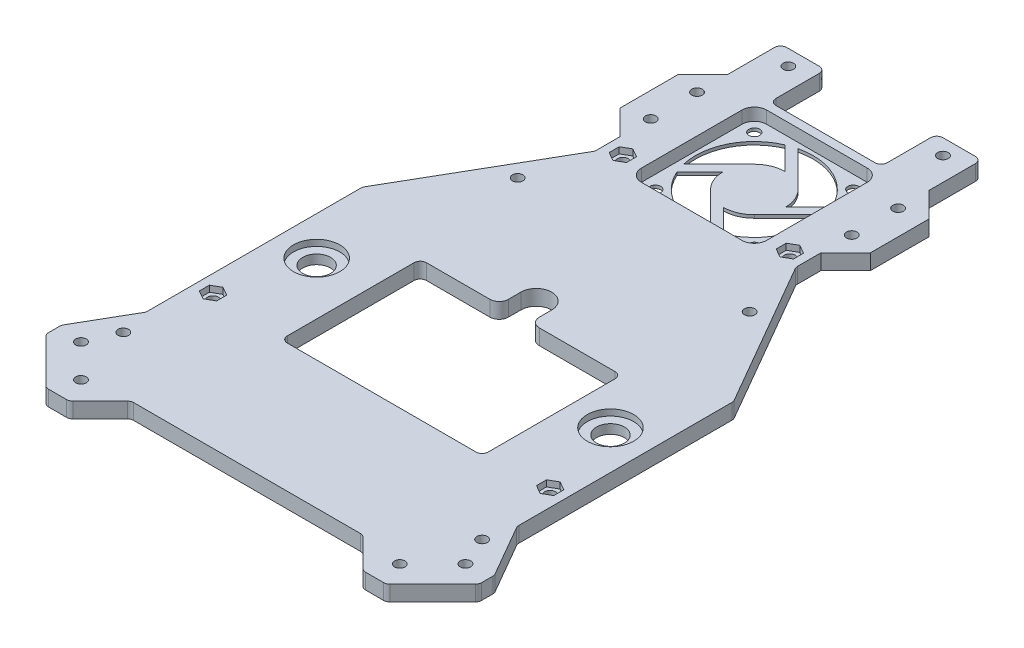
SolidWorks part; units mm, degrees
material "ABS PC"
ref_plane "Front Plane" through (0, 0, 0) normal (0, 0, 1) x (1, 0, 0)
ref_plane "Top Plane" through (0, 0, 0) normal (0, 1, 0) x (1, 0, 0)
ref_plane "Right Plane" through (0, 0, 0) normal (1, 0, 0) x (0, 0, -1)
sketch "Sketch1" plane through (0, 0, 0) normal (0, 1, 0) x (1, 0, 0)
  line L1 (70, -110) -> (-70, -110)
  line L2 (70, -110) -> (70, 110)
  line L3 (70, 110) -> (-70, 110)
  line L4 (-70, -110) -> (-70, 110)
  line L5 (70, -110) -> (-70, 110) construction
  line L6 (70, 110) -> (-70, -110) construction
  point P0 (0, 0)
  dimension "D1" = 220
  dimension "D2" = 140
extrude "Boss-Extrude1" add sketch "Sketch1" along normal blind 5
sketch "Sketch8" plane through (0, 5, 0) normal (0, 1, 0) x (1, 0, 0)
  line L0 (-70, 110) -> (-32.5, 110)
  line L1 (70, 110) -> (-70, 110) construction
  line L2 (-32.5, 110) -> (-32.5, 44.9519)
  line L3 (-32.5, 44.9519) -> (-70, -20)
  line L4 (-70, 110) -> (-70, -110) construction
  line L5 (-70, 110) -> (-70, -20)
  line L6 (0, 110) -> (0, -110) construction
  line L7 (-70, -110) -> (70, -110) construction
  line L8 (70, 110) -> (70, -20)
  line L9 (32.5, 44.9519) -> (70, -20)
  line L10 (32.5, 110) -> (32.5, 44.9519)
  line L11 (70, 110) -> (32.5, 110)
  dimension "D1" = 130
  dimension "D2" = 30
  dimension "D3" = 65
extrude "Cut-Extrude1" cut sketch "Sketch8" against normal blind 5
chamfer "Chamfer3" distance 15 angle 45 2 edges at (70, 2.5, 110) (-70, 2.5, 110)
sketch "Sketch48" plane through (0, 5, 0) normal (0, 1, 0) x (1, 0, 0)
  line L0 (32.5, 110) -> (-32.5, 110) construction
  line L1 (34.2449, 70.5) -> (40.5, 70.5) construction
  line L2 (32.5, 53) -> (32.5, 88)
  line L4 (32.5, 88) -> (40.5, 80)
  line L5 (40.5, 80) -> (40.5, 61)
  line L6 (32.5, 53) -> (40.5, 61)
  line L7 (0, 71.0199) -> (0, 60.9015) construction
  line L8 (-32.5, 53) -> (-40.5, 61)
  line L9 (-40.5, 80) -> (-40.5, 61)
  line L10 (-32.5, 88) -> (-40.5, 80)
  line L11 (-32.5, 53) -> (-32.5, 88)
  line L13 (32.5, 110) -> (32.5, 44.9519) construction
  point P16 (-32.5, 70.5)
  dimension "D1" = 45
  dimension "D2" = 8
  dimension "D3" = 35
  dimension "D4" = 39.5
extrude "Boss-Extrude4" add sketch "Sketch48" against normal up to surface (5 mm away) up to face at (0, 0, 14.0096)
sketch "Sketch10" plane through (0, 0, 0) normal (0, 1, 0) x (1, 0, 0)
  line L0 (0, 110) -> (0, -110) construction
  line L1 (32.5, 110) -> (-32.5, 110) construction
  line L2 (-55, -110) -> (55, -110) construction
  line L3 (-32.5, 78) -> (-32.5, 63) construction
  line L4 (-62.5, -102.5) -> (-56.8431, -96.8431) construction
  line L5 (-62.1464, -91.5398) -> (-51.5398, -102.1464) construction
  line L6 (-70, -95) -> (-55, -110) construction
  point P9 (32.5, 63)
  point P10 (32.5, 78)
  point P17 (51.5398, -102.1464)
  point P18 (62.1464, -91.5398)
  dimension "D1" = 15
  dimension "D2" = 65
  dimension "D3" = 32
  dimension "D4" = 15
  dimension "D5" = 8
sketch "Sketch15" plane through (0, 5, 0) normal (0, 1, 0) x (1, 0, 0)
  line L0 (0, 110) -> (0, -110) construction
  line L1 (32.5, 110) -> (-32.5, 110) construction
  line L2 (-55, -110) -> (55, -110) construction
  line L3 (25, 100) -> (-25, 100) construction
  line L4 (37.5, 25) -> (-37.5, 25) construction
  line L5 (58, -57) -> (-58, -57) construction
  point P9 (0, 100)
  point P13 (0, 25)
  point P15 (0, -57)
  dimension "D1" = 50
  dimension "D2" = 10
  dimension "D3" = 75
  dimension "D4" = 85
  dimension "D5" = 116
  dimension "D6" = 167
hole_wizard "CSK for M3 Flat Head Machine Screw3" positions "Sketch16" profile "Sketch17" countersink size "M3" standard "ANSI Metric"
sketch "Sketch16" plane through (0, 0, 0) normal (0, 1, 0) x (1, 0, 0)
  point P6 (37.5, 25)
  point P9 (-37.5, 25)
  point P12 (-25, 100)
  point P15 (25, 100)
sketch "Sketch17" plane through (37.5, 0, -25) normal (1, 0, 0) x (0, 0, -1)
  line L0 (0, 0) -> (0, 6.0215)
  line L1 (0, 6.0215) -> (1.7, 5)
  line L2 (1.7, 5) -> (1.7, 1.45)
  line L3 (1.7, 1.45) -> (3.15, 0)
  line L5 (3.15, 0) -> (0, 0)
  line L6 (-1.7, 1.45) -> (-3.15, 0) construction
  line L10 (0, 6.0215) -> (-1.7, 5) construction
  line L11 (0, -6.35) -> (0, 107.95) construction
  dimension "Hole Dia." = 3.4
  dimension "Hole Depth" = 5
  dimension "Near C'Sink Dia." = 6.3
  dimension "Near C'Sink Angle" = 90
  dimension "Drill Angle" = 118
sketch "Sketch18" plane through (0, 5, 0) normal (0, 1, 0) x (1, 0, 0)
  line L0 (32.5, 110) -> (-32.5, 110) construction
  line L1 (-46.4338, 114.6286) -> (34.8035, 114.6286)
  line L2 (-46.4338, 114.6286) -> (-46.4338, 105)
  line L3 (-46.4338, 105) -> (34.8035, 105)
  line L4 (34.8035, 114.6286) -> (34.8035, 105)
  dimension "D1" = 5
extrude "Cut-Extrude2" cut sketch "Sketch18" against normal blind 5
sketch "Sketch34" plane through (0, 5, 0) normal (0, 1, 0) x (1, 0, 0)
  line L0 (-70, -20) -> (-60, -2.6795)
  line L1 (-70, -20) -> (-32.5, 44.9519) construction
  line L2 (-60, -2.6795) -> (-60, -72.6795)
  line L3 (-60, -72.6795) -> (-70, -90)
  line L4 (-70, -20) -> (-70, -95) construction
  line L5 (-70, -90) -> (-70, -20)
  line L6 (0, -90.4055) -> (0, -61.6307) construction
  line L7 (70, -90) -> (70, -20)
  line L8 (60, -72.6795) -> (70, -90)
  line L9 (60, -2.6795) -> (60, -72.6795)
  line L10 (70, -20) -> (60, -2.6795)
  line L11 (-55, -110) -> (55, -110) construction
  dimension "D1" = 120
  dimension "D2" = 20
extrude "Cut-Extrude8" cut sketch "Sketch34" against normal blind 10
chamfer "Chamfer4" [suppressed] distance 20 angle 30
sketch "Sketch35" plane through (0, 5, 0) normal (0, 1, 0) x (1, 0, 0)
  line L1 (-30.5, -58.5) -> (34.5, -58.5)
  line L2 (-30.5, -58.5) -> (-30.5, -13.5)
  line L3 (-30.5, -13.5) -> (34.5, -13.5)
  line L4 (34.5, -58.5) -> (34.5, -13.5)
  line L5 (-30.5, -58.5) -> (34.5, -13.5) construction
  line L6 (-30.5, -13.5) -> (34.5, -58.5) construction
  point P0 (2, -36)
  dimension "D1" = 2
  dimension "D2" = 65
  dimension "D3" = 45
  dimension "D4" = 36
extrude "Cut-Extrude9" cut sketch "Sketch35" against normal through all
fillet "Fillet1" radius 2 4 edges at (-30.5, 2.5, 58.5) (-30.5, 2.5, 13.5) (34.5, 2.5, 13.5) (34.5, 2.5, 58.5)
sketch "Sketch36" plane through (0, 5, 0) normal (0, 1, 0) x (1, 0, 0)
  line L0 (0, -110) -> (0, -100) construction
  line L1 (-55, -110) -> (55, -110) construction
  line L2 (-47.5, -110) -> (-37.5, -100)
  line L3 (-37.5, -100) -> (37.5, -100)
  line L4 (-47.5, -110) -> (47.5, -110)
  line L6 (-70, -95) -> (-55, -110) construction
  line L7 (47.5, -110) -> (37.5, -100)
  dimension "D1" = 10
  dimension "D2" = 95
extrude "Cut-Extrude10" cut sketch "Sketch36" against normal through all
sketch "Sketch38" plane through (0, 0, 0) normal (0, -1, 0) x (1, 0, 0)
  line L0 (0, -105) -> (0, -90) construction
  line L1 (-32.5, -105) -> (32.5, -105) construction
  line L2 (18, -87) -> (-18, -87)
  line L3 (-18, -87) -> (-18, -105)
  line L4 (-18, -105) -> (18, -105)
  line L5 (18, -87) -> (18, -105)
  dimension "D1" = 90
  dimension "D2" = 18
  dimension "D3" = 36
extrude "Cut-Extrude14" cut sketch "Sketch38" against normal through all
sketch "Sketch39" plane through (0, 0, 0) normal (0, -1, 0) x (1, 0, 0)
  line L0 (0, 37.973) -> (0, 15.9654) construction
  circle A0 centre (-47.5, 30) radius 4.5
  circle A1 centre (47.5, 30) radius 4.5
  dimension "D1" = 95
  dimension "D2" = 9
  dimension "D3" = 30
extrude "Cut-Extrude15" cut sketch "Sketch39" against normal through all
hole_wizard "CSK for M3 Flat Head Machine Screw2" positions "Sketch40" profile "Sketch41" countersink size "M3" standard "ANSI Metric"
sketch "Sketch40" plane through (0, 0, 0) normal (0, -1, 0) x (-1, 0, 0)
  point P0 (-58, -82)
  point P3 (58, -82)
sketch "Sketch41" plane through (58, 0, 82) normal (1, 0, 0) x (0, 0, -1)
  line L0 (0, 0) -> (0, 11.0215)
  line L1 (0, 11.0215) -> (1.7, 10)
  line L2 (1.7, 10) -> (1.7, 1.45)
  line L3 (1.7, 1.45) -> (3.15, 0)
  line L5 (3.15, 0) -> (0, 0)
  line L6 (-1.7, 1.45) -> (-3.15, 0) construction
  line L10 (0, 11.0215) -> (-1.7, 10) construction
  line L11 (0, -6.35) -> (0, 107.95) construction
  dimension "Hole Dia." = 3.4
  dimension "Hole Depth" = 10
  dimension "Near C'Sink Dia." = 6.3
  dimension "Near C'Sink Angle" = 90
  dimension "Drill Angle" = 118
hole_wizard "Ø3.5 (3.5) Diameter Hole1" positions "Sketch45" profile "Sketch46" hole size "Ø3.5" standard "ANSI Metric"
sketch "Sketch45" plane through (0, 5, 0) normal (0, 1, 0) x (1, 0, 0)
  line L0 (-32.5, 44.9519) -> (-32.5, 53) construction
  line L1 (-60, -72.6795) -> (-60, -2.6795) construction
  line L2 (-32.5, 105) -> (-18, 105) construction
  point P0 (-54.5, -56.5)
  point P2 (-27, 48.5)
  dimension "D1" = 5.5
  dimension "D2" = 5.5
  dimension "D3" = 56.5
  dimension "D4" = 105
sketch "Sketch46" plane through (-54.5, 5, 56.5) normal (1, 0, 0) x (0, 0, 1)
  line L0 (0, 0) -> (0, 6.0515)
  line L1 (0, 6.0515) -> (1.75, 5)
  line L2 (1.75, 5) -> (1.75, 0)
  line L5 (1.75, 0) -> (0, 0)
  line L10 (0, 6.0515) -> (-1.75, 5) construction
  line L11 (0, -6.35) -> (0, 107.95) construction
  dimension "Hole Dia." = 3.5
  dimension "Hole Depth" = 5
  dimension "Drill Angle" = 118
mirror "Mirror1" about plane through (0, 0, 0) normal (1, 0, 0) of "Ø3.5 (3.5) Diameter Hole1"
sketch "Sketch47" plane through (0, 5, 0) normal (0, 1, 0) x (1, 0, 0)
  line L0 (0, 13.2168) -> (0, -3.9151) construction
  line L1 (29.8, 46.8834) -> (29.8, 50.1166)
  line L2 (29.8, 50.1166) -> (27, 51.7332)
  line L3 (27, 51.7332) -> (24.2, 50.1166)
  line L4 (24.2, 50.1166) -> (24.2, 46.8834)
  line L5 (24.2, 46.8834) -> (27, 45.2668)
  line L6 (27, 45.2668) -> (29.8, 46.8834)
  line L7 (57.3, -58.1166) -> (57.3, -54.8834)
  line L8 (57.3, -54.8834) -> (54.5, -53.2668)
  line L9 (54.5, -53.2668) -> (51.7, -54.8834)
  line L10 (51.7, -54.8834) -> (51.7, -58.1166)
  line L11 (51.7, -58.1166) -> (54.5, -59.7332)
  line L12 (54.5, -59.7332) -> (57.3, -58.1166)
  line L13 (-54.5, -59.7332) -> (-57.3, -58.1166)
  line L14 (-51.7, -58.1166) -> (-54.5, -59.7332)
  line L15 (-51.7, -54.8834) -> (-51.7, -58.1166)
  line L16 (-54.5, -53.2668) -> (-51.7, -54.8834)
  line L17 (-57.3, -54.8834) -> (-54.5, -53.2668)
  line L18 (-57.3, -58.1166) -> (-57.3, -54.8834)
  line L19 (-27, 45.2668) -> (-29.8, 46.8834)
  line L20 (-24.2, 46.8834) -> (-27, 45.2668)
  line L21 (-24.2, 50.1166) -> (-24.2, 46.8834)
  line L22 (-27, 51.7332) -> (-24.2, 50.1166)
  line L23 (-29.8, 50.1166) -> (-27, 51.7332)
  line L24 (-29.8, 46.8834) -> (-29.8, 50.1166)
  circle A0 centre (27, 48.5) radius 2.8 construction
  circle A1 centre (54.5, -56.5) radius 2.8 construction
  circle A2 centre (-54.5, -56.5) radius 2.8 construction
  circle A3 centre (-27, 48.5) radius 2.8 construction
  dimension "D1" = 5.6
extrude "Cut-Extrude16" cut sketch "Sketch47" against normal blind 2
hole_wizard "CSK for M3 Flat Head Machine Screw1" positions "Sketch52" profile "Sketch53" countersink size "M3" standard "ANSI Metric"
sketch "Sketch52" plane through (0, 0, 0) normal (0, -1, 0) x (-1, 0, 0)
  point P0 (32.5, 63)
  point P3 (32.5, 78)
  point P6 (-32.5, 78)
  point P9 (-32.5, 63)
  point P12 (62.1464, -91.5398)
  point P15 (51.5398, -102.1464)
  point P18 (-51.5398, -102.1464)
  point P21 (-62.1464, -91.5398)
sketch "Sketch53" plane through (-32.5, 0, -63) normal (1, 0, 0) x (0, 0, -1)
  line L0 (0, 0) -> (0, 6.0215)
  line L1 (0, 6.0215) -> (1.7, 5)
  line L2 (1.7, 5) -> (1.7, 1.45)
  line L3 (1.7, 1.45) -> (3.15, 0)
  line L5 (3.15, 0) -> (0, 0)
  line L6 (-1.7, 1.45) -> (-3.15, 0) construction
  line L10 (0, 6.0215) -> (-1.7, 5) construction
  line L11 (0, -6.35) -> (0, 107.95) construction
  dimension "Hole Dia." = 3.4
  dimension "Hole Depth" = 5
  dimension "Near C'Sink Dia." = 6.3
  dimension "Near C'Sink Angle" = 90
  dimension "Drill Angle" = 118
fillet "Fillet3" radius 2 22 edges at (-32.5, 2.5, -105) (-32.5, 2.5, -44.9519) (-60, 2.5, 2.6795) (-60, 2.5, 72.6795) (-70, 2.5, 90) (-70, 2.5, 95) (-55, 2.5, 110) (-47.5, 2.5, 110) (-37.5, 2.5, 100) (37.5, 2.5, 100) (47.5, 2.5, 110) (55, 2.5, 110) (70, 2.5, 95) (70, 2.5, 90) (60, 2.5, 72.6795) (60, 2.5, 2.6795) (32.5, 2.5, -44.9519) (18, 2.5, -105) (18, 2.5, -87) (-18, 2.5, -87) (-18, 2.5, -105) (32.5, 2.5, -105)
sketch "Sketch54" plane through (0, 5, 0) normal (0, 1, 0) x (1, 0, 0)
  line L0 (0, -24.4413) -> (0, -37.1235) construction
  circle A0 centre (-47.5, -30) radius 7.5
  circle A1 centre (-47.5, -30) radius 4.5
  circle A2 centre (-47.5, -30) radius 4.5 construction
  circle A3 centre (47.5, -30) radius 4.5
  circle A4 centre (47.5, -30) radius 7.5
  dimension "D1" = 15
extrude "Cut-Extrude17" cut sketch "Sketch54" against normal blind 2
hole_wizard "Ø3.5 (3.5) Diameter Hole2" positions "Sketch55" profile "Sketch56" hole size "Ø3.5" standard "ANSI Metric" end condition through all
sketch "Sketch55" plane through (0, 5, 0) normal (0, 1, 0) x (1, 0, 0)
  line L1 (16, 80) -> (-16, 80) construction
  line L2 (16, 80) -> (16, 48) construction
  line L3 (16, 48) -> (-16, 48) construction
  line L4 (-16, 80) -> (-16, 48) construction
  line L5 (0, 48) -> (0, 0) construction
  point P1 (16, 80)
  point P2 (-16, 48)
  point P5 (16, 48)
  point P6 (-16, 80)
  dimension "D1" = 32
  dimension "D2" = 48
sketch "Sketch56" plane through (16, 5, -80) normal (1, 0, 0) x (0, 0, 1)
  line L0 (0, 0) -> (0, 5)
  line L1 (0, 5) -> (1.75, 5)
  line L2 (1.75, 5) -> (1.75, 0)
  line L5 (1.75, 0) -> (0, 0)
  line L11 (0, -6.35) -> (0, 107.95) construction
  dimension "Thru Hole Dia." = 3.5
  dimension "Thru Hole Depth" = 5
sketch "Sketch57" plane through (0, 5, 0) normal (0, 1, 0) x (1, 0, 0)
  line L0 (-16, 80) -> (16, 48) construction
  line L1 (9.9995, 64.1) -> (17.4397, 71.5402)
  line L2 (7.0711, 56.9289) -> (18.4947, 68.3526)
  line L3 (0.1, 54.0005) -> (7.5402, 46.5603)
  line L4 (-7.0711, 56.9289) -> (4.3526, 45.5053)
  line L5 (-9.9995, 63.9) -> (-17.4397, 56.4598)
  line L6 (-7.0711, 71.0711) -> (-18.4947, 59.6474)
  line L7 (-0.1, 73.9995) -> (-7.5402, 81.4397)
  line L8 (7.0711, 71.0711) -> (-4.3526, 82.4947)
  line L9 (0, 58.5149) -> (0, 69.4851) construction
  circle A0 centre (0, 64) radius 19
  circle A1 centre (0, 64) radius 10
  point P31 (0, 64)
  dimension "D1" = 38
  dimension "D2" = 20
  dimension "D3" = 3
  dimension "D5" = 135
  dimension "D4" = 4
extrude "Cut-Extrude18" cut sketch "Sketch57" against normal blind 10 contours A1 L7 A0 L6 | A1 L1 A0 L8 | A1 L3 A0 L2 | A1 L5 A0 L4 region at (7.9912, 5, -75.4298) region at (11.4298, 5, -56.0088) region at (-11.4298, 5, -71.9912) region at (-7.9912, 5, -52.5702)
sketch "Sketch58" plane through (0, 5, 0) normal (0, 1, 0) x (1, 0, 0)
  line L1 (-16.25, 43.75) -> (16.25, 43.75)
  line L2 (-20.25, 47.75) -> (-20.25, 80.25)
  line L3 (-16.25, 84.25) -> (16.25, 84.25)
  line L4 (20.25, 47.75) -> (20.25, 80.25)
  line L5 (-20.25, 43.75) -> (20.25, 84.25) construction
  line L6 (-20.25, 84.25) -> (20.25, 43.75) construction
  arc A0 (-20.25, 47.75) -> (-16.25, 43.75) centre (-16.25, 47.75) ccw
  arc A1 (16.25, 43.75) -> (20.25, 47.75) centre (16.25, 47.75) ccw
  arc A2 (20.25, 80.25) -> (16.25, 84.25) centre (16.25, 80.25) ccw
  arc A3 (-16.25, 84.25) -> (-20.25, 80.25) centre (-16.25, 80.25) ccw
  point P0 (0, 64)
  dimension "D2" = 4
  dimension "D1" = 40.5
extrude "Cut-Extrude20" cut sketch "Sketch58" against normal blind 4
sketch "Sketch59" plane through (0, 0, 0) normal (0, -1, 0) x (1, 0, 0)
  line L0 (32.5, 13.5) -> (-28.5, 13.5) construction
  line L1 (5, 6.5) -> (-5, 6.5)
  line L2 (5, 6.5) -> (5, 13.5)
  line L3 (5, 13.5) -> (-5, 13.5)
  line L4 (-5, 6.5) -> (-5, 13.5)
  line L5 (5, 6.5) -> (-5, 13.5) construction
  line L6 (5, 13.5) -> (-5, 6.5) construction
  line L7 (0, 0) -> (0, 10) construction
  arc A0 (-5, 6.5) -> (5, 6.5) centre (0, 6.5) ccw
  point P0 (0, 10)
  dimension "D1" = 7
  dimension "D2" = 10
extrude "Cut-Extrude21" cut sketch "Sketch59" against normal blind 10 contours L4 L1 L2 L3 | L1 A0 region at (0, 0, 4.3779) region at (0, 0, 10)
fillet "Fillet5" radius 3 2 edges at (5, 2.5, 13.5) (-5, 2.5, 13.5)
